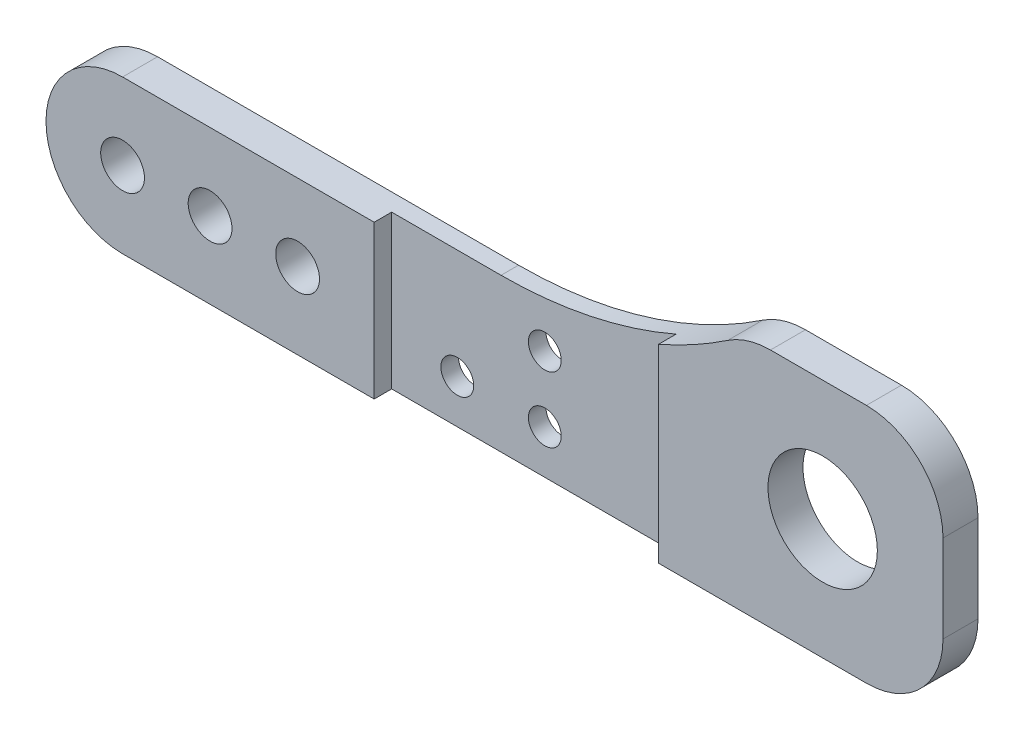
SolidWorks part; units mm, degrees
ref_plane "Front Plane" through (0, 0, 0) normal (0, 0, 1) x (1, 0, 0)
ref_plane "Top Plane" through (0, 0, 0) normal (0, 1, 0) x (1, 0, 0)
ref_plane "Right Plane" through (0, 0, 0) normal (1, 0, 0) x (0, 0, -1)
sketch "Sketch1" plane through (0, 0, 0) normal (0, 0, 1) x (1, 0, 0)
  line L0 (0, 7) -> (33, 7)
  line L1 (68, -7) -> (0, -7)
  line L5 (59.2298, 15) -> (68, 15)
  line L6 (75, 0) -> (75, 8)
  arc A1 (0, -7) -> (0, 7) centre (0, 0) cw
  arc A2 (33, 7) -> (55.3232, 13.8085) centre (33, 47) ccw
  arc A3 (68, -7) -> (75, 0) centre (68, 0) ccw
  arc A4 (68, 15) -> (75, 8) centre (68, 8) cw
  arc A5 (59.2298, 15) -> (55.3232, 13.8085) centre (59.2298, 8) ccw
  point P3 (75, -7)
  point P15 (75, 15)
  point P18 (57, 15)
  dimension "D2" = 7
  dimension "D4" = 40
  dimension "D1" = 7
  dimension "D3" = 22
  dimension "D5" = 18
  dimension "D6" = 75
extrude "Boss-Extrude1" add sketch "Sketch1" along normal blind 3.2
sketch "Sketch2" plane through (0, 0, 3.2) normal (0, 0, 1) x (1, 0, 0)
  line L0 (-7, 0) -> (-7, -7) construction
  line L6 (0, 0) -> (8, 0) construction
  line L7 (8, 0) -> (16, 0) construction
  line L8 (-7, -7) -> (0, -7) construction
  circle A0 centre (0, 0) radius 2
  circle A2 centre (8, 0) radius 2
  circle A5 centre (16, 0) radius 2
  arc A6 (0, 7) -> (0, -7) centre (0, 0) ccw construction
  dimension "D1" = 4
  dimension "D2" = 8
extrude "Cut-Extrude1" cut sketch "Sketch2" against normal up to surface (3.2 mm away) up to face at (47.7635, 5.6039, 0)
sketch "Sketch3" plane through (0, 0, 3.2) normal (0, 0, 1) x (1, 0, 0)
  line L0 (75, 0) -> (75, 8) construction
  line L2 (64, 4) -> (75, 4) construction
  line L3 (64, 4) -> (64, -7) construction
  line L4 (0, -7) -> (68, -7) construction
  circle A0 centre (64, 4) radius 5
  dimension "D1" = 10
extrude "Cut-Extrude2" cut sketch "Sketch3" against normal up to surface (3.2 mm away) up to face at (2, 0, 0)
sketch "Sketch4" plane through (0, 0, 3.2) normal (0, 0, -1) x (-1, 0, 0)
  line L0 (0, -7) -> (-68, -7) construction
  line L1 (-49, -7) -> (-23, -7)
  line L2 (-49, -7) -> (-49, 10.3394)
  line L3 (-49, 10.3394) -> (-23, 10.3394)
  line L4 (-23, -7) -> (-23, 10.3394)
  line L5 (-75, 0) -> (-75, 8) construction
  arc A0 (-55.3232, 13.8085) -> (-33, 7) centre (-33, 47) ccw construction
  dimension "D1" = 26
  dimension "D2" = 26
extrude "Cut-Extrude3" cut sketch "Sketch4" along normal blind 1.6
hole_wizard "Ø3.0mm Dowel Hole2" positions "Sketch9" profile "Sketch10" hole size "Ø3.0" standard "ANSI Metric" end condition through all
sketch "Sketch9" plane through (0, 0, 1.6) normal (0, 0, 1) x (1, 0, 0)
  line L0 (49, -7) -> (23, -7) construction
  line L1 (23, -7) -> (23, 7) construction
  point P0 (29, -3)
  point P3 (37, -3)
  point P6 (37, 3)
  point P14 (0, 0)
  point P15 (0, 0)
  point P16 (0, 0)
  dimension "D1" = 6
  dimension "D2" = 8
  dimension "D3" = 4
  dimension "D4" = 6
sketch "Sketch10" plane through (29, -3, 1.6) normal (1, 0, 0) x (0, -1, 0)
  line L0 (0, 0) -> (0, 1.6)
  line L1 (0, 1.6) -> (1.5, 1.6)
  line L2 (1.5, 1.6) -> (1.5, 0)
  line L5 (1.5, 0) -> (0, 0)
  line L11 (0, -6.35) -> (0, 107.95) construction
  dimension "Thru Hole Dia." = 3
  dimension "Thru Hole Depth" = 1.6
